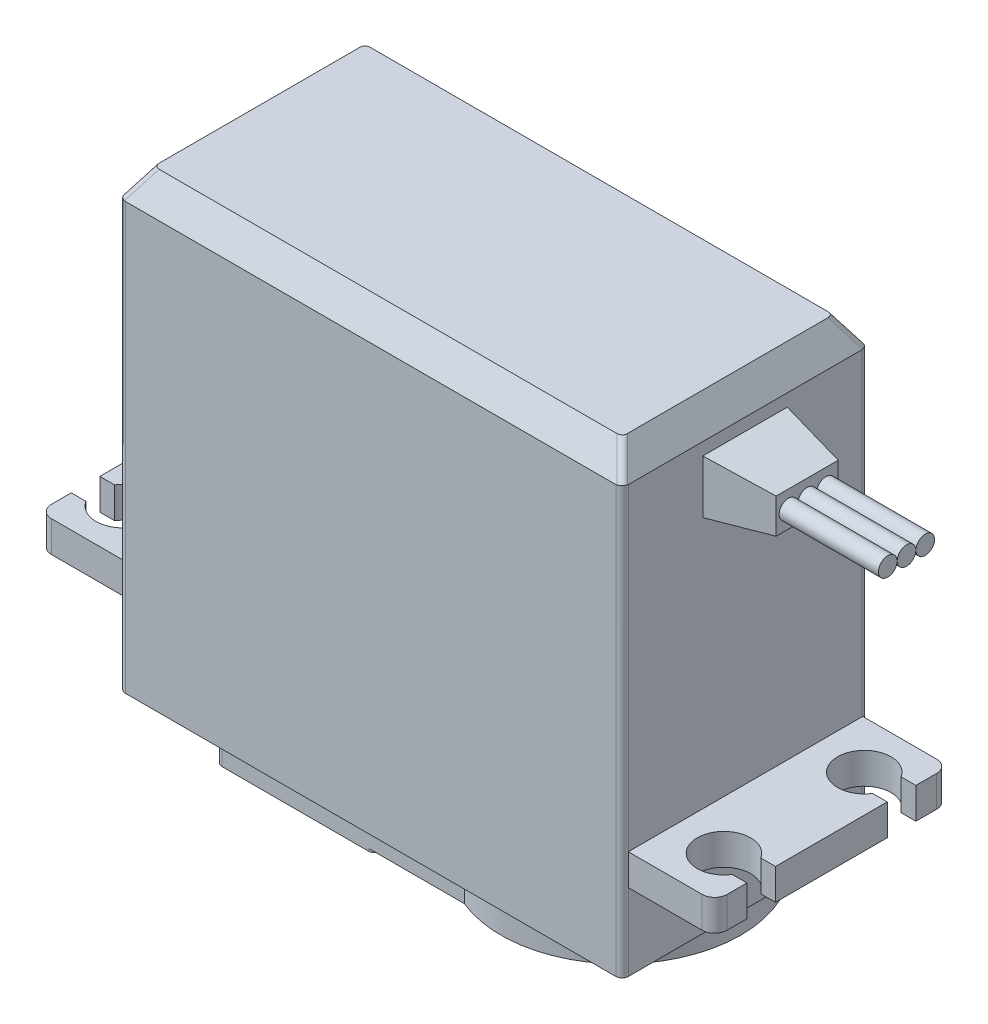
SolidWorks part; units mm, degrees
ref_plane "Front" through (0, 0, 0) normal (0, 0, 1) x (1, 0, 0)
ref_plane "Top" through (0, 0, 0) normal (0, 1, 0) x (1, 0, 0)
ref_plane "Right" through (0, 0, 0) normal (1, 0, 0) x (0, 0, -1)
sketch "Sketch 1" plane through (0, 0, 0) normal (0, 1, 0) x (1, 0, 0)
  line L1 (20.25, -9.9) -> (-20.25, -9.9)
  line L2 (20.25, -9.9) -> (20.25, 9.9)
  line L3 (20.25, 9.9) -> (-20.25, 9.9)
  line L4 (-20.25, -9.9) -> (-20.25, 9.9)
  line L5 (0, 9.9) -> (0, -9.9) construction
  line L6 (20.25, 0) -> (-20.25, 0) construction
  point P0 (0, 0)
  dimension "D1" = 19.8
  dimension "D2" = 40.5
extrude "Body" add sketch "Sketch 1" along normal blind 36.5
chamfer "Chamfer" distance 2.2 distance2 1.4 4 edges at (-20.25, 36.5, 0) (0, 36.5, -9.9) (20.25, 36.5, 0) (0, 36.5, 9.9) first distance on face at (-20.25, 18.25, 0) first distance on face at (0, 18.25, -9.9) first distance on face at (20.25, 18.25, 0) first distance on face at (0, 18.25, 9.9)
fillet "Fillet" radius 0.5 8 edges at (-20.25, 17.15, -9.9) (-19.55, 35.4, -9.2) (19.55, 35.4, -9.2) (20.25, 17.15, -9.9) (19.55, 35.4, 9.2) (-19.55, 35.4, 9.2) (20.25, 17.15, 9.9) (-20.25, 17.15, 9.9)
ref_plane "Palne" through (0, 6.2, 0) normal (0, -1, 0) x (-1, 0, 0)
sketch "Sketch 2" plane through (0, 6.2, 0) normal (0, -1, 0) x (-1, 0, 0)
  line L0 (-19.75, 9.9) -> (19.75, 9.9) construction
  line L1 (-26.2, 9.4728) -> (26.2, 9.4728)
  line L2 (27.2, -8.4) -> (27.2, -6.8)
  line L3 (-26.2, -9.4) -> (26.2, -9.4)
  line L4 (-27.2, -8.4) -> (-27.2, -6.8)
  line L5 (0, 9.9) -> (0, -9.9) construction
  line L6 (27.2, 0) -> (-27.2, 0) construction
  line L7 (-24.2, 5.65) -> (-27.2, 5.65) construction
  line L8 (-26.0166, 6.8) -> (-27.2, 6.8)
  line L9 (-26.0166, 4.5) -> (-27.2, 4.5)
  line L10 (-27.2, 6.8) -> (-27.2, 8.4728)
  line L11 (-26.0166, -4.5) -> (-27.2, -4.5)
  line L12 (-26.0166, -6.8) -> (-27.2, -6.8)
  line L13 (26.0166, -6.8) -> (27.2, -6.8)
  line L14 (26.0166, -4.5) -> (27.2, -4.5)
  line L15 (26.0166, 4.5) -> (27.2, 4.5)
  line L16 (26.0166, 6.8) -> (27.2, 6.8)
  line L17 (27.2, 6.8) -> (27.2, 8.4728)
  line L18 (27.2, -4.5) -> (27.2, 4.5)
  line L19 (-27.2, -4.5) -> (-27.2, 4.5)
  arc A0 (27.2, -8.4) -> (26.2, -9.4) centre (26.2, -8.4) cw
  arc A1 (26.2, 9.4728) -> (27.2, 8.4728) centre (26.2, 8.4728) cw
  arc A2 (-27.2, -8.4) -> (-26.2, -9.4) centre (-26.2, -8.4) ccw
  arc A3 (-27.2, 8.4728) -> (-26.2, 9.4728) centre (-26.2, 8.4728) cw
  arc A4 (-26.0166, 4.5) -> (-26.0166, 6.8) centre (-24.2, 5.65) ccw
  arc A5 (-26.0166, -4.5) -> (-26.0166, -6.8) centre (-24.2, -5.65) cw
  arc A6 (26.0166, -4.5) -> (26.0166, -6.8) centre (24.2, -5.65) ccw
  arc A7 (26.0166, 4.5) -> (26.0166, 6.8) centre (24.2, 5.65) cw
  point P0 (0, 0)
  point P10 (27.2, 9.9)
  point P16 (-27.2, 9.9)
  dimension "D2" = 1
  dimension "D4" = 4.3
  dimension "D1" = 54.4
  dimension "D5" = 3
  dimension "D6" = 1.15
extrude "Mount" add sketch "Sketch 2" against normal blind 2.5 contours L15 A7 L16 L17 A1 L1 A3 L10 L8 A4 L9 L4 L11 A5 L12 A2 L3 A0 L2 L13 A6 L14 L18 region at (0, 6.2, -0.039)
sketch "Sketch 3" plane through (0, 0, 0) normal (0, 0, 1) x (1, 0, 0)
  line L0 (-27.2, 6.2) -> (-20.25, 6.2)
  line L1 (-20.25, 6.2) -> (-20.25, 5.2)
  line L2 (-20.25, 0) -> (-20.25, 6.2) construction
  line L3 (-20.25, 5.2) -> (-27.2, 6.2)
  line L4 (0, 0) -> (0, 36.5) construction
  line L5 (-18.4282, 36.5) -> (18.4282, 36.5) construction
  line L6 (20.25, 5.2) -> (27.2, 6.2)
  line L7 (20.25, 6.2) -> (20.25, 5.2)
  line L8 (27.2, 6.2) -> (20.25, 6.2)
  dimension "D1" = 1
extrude "Extrude" add sketch "Sketch 3" along normal mid plane 1
sketch "Sketch 4" plane through (0, 0, 0) normal (0, -1, 0) x (1, 0, 0)
  line L0 (20.25, 9.4) -> (20.25, -9.4) construction
  line L1 (-13.4526, -8.92) -> (-13.4526, -4.6)
  line L2 (-13.4526, -8.92) -> (6.5681, -8.92)
  line L3 (-13.4526, 8.92) -> (6.5681, 8.92)
  line L4 (-20.25, 0.5) -> (-20.25, -0.5) construction
  line L6 (-13.4526, 4.6) -> (-13.4526, 8.92)
  arc A0 (6.5681, -8.92) -> (6.5681, 8.92) centre (10.25, 0) ccw
  arc A1 (-13.4526, 4.6) -> (-13.4526, -4.6) centre (-11.493, 0) ccw
  point P2 (20.25, 0)
  point P6 (3.35, 0)
  dimension "D1" = 19.3
  dimension "D5" = 5
  dimension "D2" = 10
  dimension "D3" = 17.84
  dimension "D4" = 9.2
extrude "Extrude 2" add sketch "Sketch 4" along normal blind 2
sketch "Sketch 5" plane through (0, -2, 0) normal (0, -1, 0) x (1, 0, 0)
  line L0 (-13.4526, -8.92) -> (6.5681, -8.92) construction
  line L1 (-13.4526, 8.92) -> (-0.6526, 8.92)
  line L2 (-13.4526, 8.92) -> (-13.4526, -8.92)
  line L3 (-13.4526, -8.92) -> (-0.6526, -8.92)
  line L4 (-0.6526, 8.92) -> (-0.6526, 2)
  line L5 (-0.6526, -2) -> (-0.6526, -8.92)
  line L7 (-1.6526, -7.92) -> (-12.4526, -7.92)
  line L8 (-1.6526, -7.92) -> (-1.6526, 7.92)
  line L9 (-1.6526, 7.92) -> (-12.4526, 7.92)
  line L10 (-12.4526, -7.92) -> (-12.4526, 7.92)
  line L11 (-7.0526, 7.92) -> (-7.0526, -7.92) construction
  line L12 (-1.6526, 0) -> (-12.4526, 0) construction
  arc A0 (-0.6526, 2) -> (-0.6526, -2) centre (-0.6526, 0) cw
  point P10 (-7.0526, 0)
  dimension "D2" = 2
  dimension "D1" = 12.8
  dimension "D3" = 1
  dimension "D4" = 15.84
  dimension "D5" = 10.8
extrude "Extrude 3" add sketch "Sketch 5" along normal blind 0.2
sketch "Sketch 6" plane through (0, -2, 0) normal (0, -1, 0) x (1, 0, 0)
  circle A0 centre (10.25, 0) radius 6.6
  dimension "D1" = 13.2
extrude "Extrude 4" add sketch "Sketch 6" along normal blind 1.2
sketch "Sketch 7" plane through (0, -3.2, 0) normal (0, -1, 0) x (1, 0, 0)
  circle A0 centre (10.25, 0) radius 5.35
  dimension "D1" = 10.7
extrude "Extrude 5" add sketch "Sketch 7" along normal blind 0.5
sketch "Sketch 8" plane through (0, -3.7, 0) normal (0, -1, 0) x (1, 0, 0)
  circle A0 centre (10.25, 0) radius 2.6
  dimension "D1" = 5.2
extrude "Shaft hole" cut sketch "Sketch 8" against normal blind 10
fillet "Fillet 2" radius 0.5 10 edges at (-13.4526, -1.1, 8.92) (-0.6526, -2.1, 2) (-0.6526, -2.1, -2) (-13.4526, -1.1, -8.92) (-1.6526, -2.1, 7.92) (-1.6526, -2.1, -7.92) (-12.4526, -2.1, 7.92) (-12.4526, -2.1, -7.92)
sketch "Sketch 10" plane through (20.25, 0, 0) normal (1, 0, 0) x (0, 0, -1)
  line L0 (-8.0782, 36.5) -> (8.0782, 36.5) construction
  line L1 (-3.4, 33.3) -> (3.4, 33.3)
  line L2 (-3.4, 33.3) -> (-3.4, 29)
  line L3 (-3.4, 29) -> (3.4, 29)
  line L4 (3.4, 33.3) -> (3.4, 29)
  line L5 (0, 29) -> (0, 33.3) construction
  line L6 (-3.4, 31.15) -> (3.4, 31.15) construction
  point P0 (0, 31.15)
  dimension "D1" = 3.2
  dimension "D2" = 6.8
  dimension "D3" = 4.3
ref_plane "plane 2" through (25.25, 0, 0) normal (1, 0, 0) x (0, 0, -1)
sketch "sketch 9" plane through (25.25, 0, 0) normal (1, 0, 0) x (0, 0, -1)
  line L1 (-2.5, 29.75) -> (2.5, 29.75)
  line L2 (-2.5, 29.75) -> (-2.5, 32.55)
  line L3 (-2.5, 32.55) -> (2.5, 32.55)
  line L4 (2.5, 29.75) -> (2.5, 32.55)
  line L5 (0, 32.55) -> (0, 29.75) construction
  line L6 (-2.5, 31.15) -> (2.5, 31.15) construction
  point P0 (0, 31.15)
  dimension "D1" = 2.8
  dimension "D2" = 5
loft "Loft" add profiles "sketch 9", "Sketch 10" connector at (25.25, 32.55, 2.5) connector at (20.25, 33.3, 3.4)
sketch "Sketch 11" plane through (25.25, 0, 0) normal (1, 0, 0) x (0, 0, -1)
  circle A0 centre (0, 31.1505) radius 0.75
  circle A1 centre (1.51, 31.15) radius 0.75
  circle A2 centre (-1.51, 31.15) radius 0.75
  dimension "D1" = 1.5
  dimension "D2" = 1.51
  dimension "D3" = 1.51
extrude "Extrude 6" add sketch "Sketch 11" along normal blind 8
